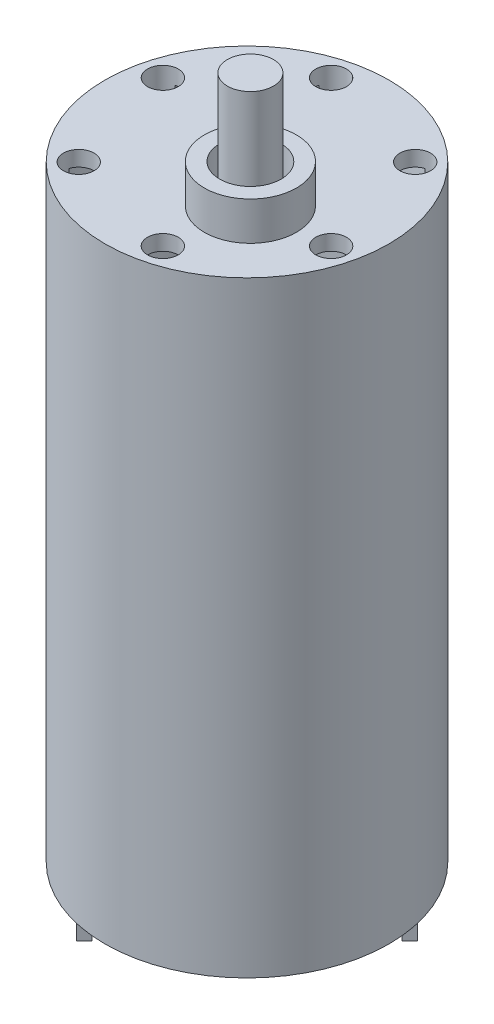
SolidWorks part; units mm, degrees
ref_plane "前视基准面" through (0, 0, 0) normal (0, 0, 1) x (1, 0, 0)
ref_plane "上视基准面" through (0, 0, 0) normal (0, 1, 0) x (1, 0, 0)
ref_plane "右视基准面" through (0, 0, 0) normal (1, 0, 0) x (0, 0, -1)
sketch "草图1" plane through (0, 0, 0) normal (0, 1, 0) x (1, 0, 0)
  circle A0 centre (0, 0) radius 18.5
  dimension "D1" = 37
extrude "凸台-拉伸1" add sketch "草图1" along normal blind 77
sketch "草图2" plane through (0, 77, 0) normal (0, 1, 0) x (1, 0, 0)
  circle A0 centre (5.1663, -4.7233) radius 6
  circle A1 centre (0, 0) radius 18.5 construction
  dimension "D2" = 12
  dimension "D1" = 7
extrude "凸台-拉伸2" add sketch "草图2" along normal blind 5
shell "抽壳1" thickness 2 removed face at (5.1663, 82, 10.7233)
sketch "草图3" plane through (0, 0, 0) normal (0, -1, 0) x (1, 0, 0)
  line L0 (0, 0) -> (31.736, 0) construction
  line L1 (9, 1.5) -> (7, 0)
  line L2 (11, 1.5) -> (9, 1.5)
  line L3 (11, 1.5) -> (11, -1.5)
  line L4 (11, -1.5) -> (9, -1.5)
  line L6 (11, 1.5) -> (9, -1.5) construction
  line L7 (11, -1.5) -> (9, 1.5) construction
  line L8 (7, 0) -> (9, -1.5)
  point P0 (10, 0)
  dimension "D1" = 10
  dimension "D2" = 2
  dimension "D3" = 3
extrude "切除-拉伸1" cut sketch "草图3" against normal blind 5
pattern_circular "阵列(圆周)1" count 4 over 360 about axis through (0, 77, 0) along (0, -1, 0) of "切除-拉伸1"
sketch "草图4" plane through (0, 0, 0) normal (0, -1, 0) x (1, 0, 0)
  circle A0 centre (0, 0) radius 18.5 construction
  circle A1 centre (0, 0) radius 18.5
  circle A2 centre (0, 0) radius 18
  dimension "D1" = 36
extrude "凸台-拉伸3" add sketch "草图4" along normal blind 2
sketch "草图5" plane through (0, 0, 0) normal (0, -1, 0) x (1, 0, 0)
  line L0 (0, 0) -> (16.3928, -16.3928) construction
  line L1 (0, 0) -> (16.9133, 0) construction
  line L2 (11.3137, -11.3137) -> (13.435, -9.1924)
  line L3 (13.435, -9.1924) -> (12.0208, -7.7782)
  line L4 (12.0208, -7.7782) -> (7.7782, -12.0208)
  line L5 (7.7782, -12.0208) -> (9.1924, -13.435)
  line L6 (9.1924, -13.435) -> (11.3137, -11.3137)
  line L8 (0, 0) -> (0, 24.1638) construction
  dimension "D1" = 135
  dimension "D2" = 2
  dimension "D3" = 3
  dimension "D4" = 3
  dimension "D5" = 14
extrude "凸台-拉伸4" add sketch "草图5" along normal blind 2
sketch "草图6" plane through (0, -2, 0) normal (0, -1, 0) x (1, 0, 0)
  line L8 (9.1924, -13.0108) -> (13.0108, -9.1924)
  line L9 (13.0108, -9.1924) -> (12.0208, -8.2024)
  line L10 (12.0208, -8.2024) -> (8.2024, -12.0208)
  line L11 (8.2024, -12.0208) -> (9.1924, -13.0108)
  line L12 (9.1924, -13.0108) -> (13.0108, -9.1924)
  line L13 (13.0108, -9.1924) -> (12.0208, -8.2024)
  line L14 (12.0208, -8.2024) -> (8.2024, -12.0208)
  line L15 (8.2024, -12.0208) -> (9.1924, -13.0108)
  dimension "D1" = 0.3
extrude "凸台-拉伸5" add sketch "草图6" along normal blind 7
sketch "草图7" plane through (11.1016, 0, -11.1016) normal (0.7071, 0, -0.7071) x (-0.7071, 0, -0.7071)
  line L0 (2.7, -9) -> (-2.7, -9) construction
  circle A0 centre (0, -5) radius 2
  dimension "D2" = 4
  dimension "D1" = 4
extrude "切除-拉伸2" cut sketch "草图7" against normal blind 7
ref_axis "基准轴1" through (0, 77, 0) along (0, -1, 0)
ref_plane "基准面1" through (0, 0, 0) normal (-0.7071, 0, 0.7071) x (0.7071, 0, 0.7071)
mirror "镜向1" about plane through (0, 0, 0) normal (-0.7071, 0, 0.7071) of "凸台-拉伸4", "切除-拉伸2", "凸台-拉伸5"
sketch "草图8" plane through (0, 75, 0) normal (0, -1, 0) x (1, 0, 0)
  circle A2 centre (5.1663, 4.7233) radius 3
  dimension "D1" = 6
extrude "凸台-拉伸6" add sketch "草图8" against normal blind 17
sketch "草图10" plane through (0, 77, 0) normal (0, 1, 0) x (1, 0, 0)
  line L0 (0, 0) -> (16.5473, -16.5473) construction
  line L1 (-6.6114, 6.6114) -> (6.6114, -6.6114) construction
  line L2 (0, 0) -> (19.1913, -5.1423) construction
  circle A0 centre (14.9719, -4.0117) radius 2
  dimension "D2" = 4
  dimension "D1" = 30
  dimension "D3" = 15.5
extrude "切除-拉伸3" cut sketch "草图10" against normal blind 10
pattern_circular "阵列(圆周)2" count 6 over 360 about axis through (0, 77, 0) along (0, -1, 0) of "切除-拉伸3"
